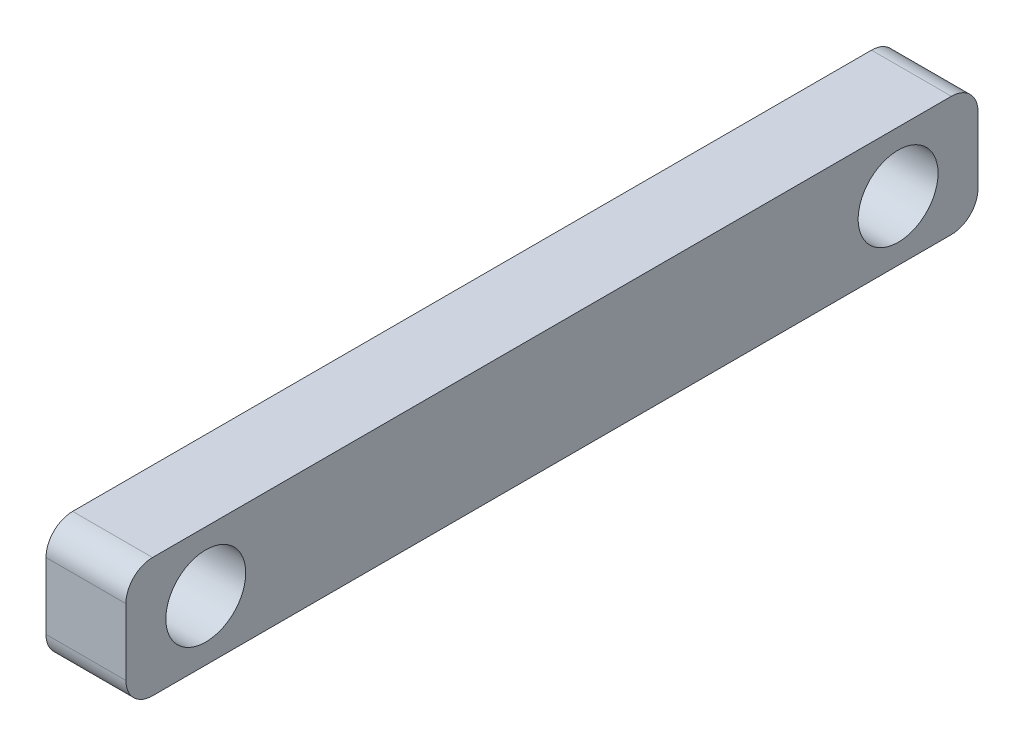
SolidWorks part; units mm, degrees
ref_plane "Alzado" through (0, 0, 0) normal (0, 0, 1) x (1, 0, 0)
ref_plane "Planta" through (0, 0, 0) normal (0, 1, 0) x (1, 0, 0)
ref_plane "Vista lateral" through (0, 0, 0) normal (1, 0, 0) x (0, 0, -1)
sketch "Croquis1" plane through (0, 0, 0) normal (1, 0, 0) x (0, 0, -1)
  line L0 (-15, 2.25) -> (15, 2.25)
  line L2 (-16, 0) -> (16, 0) construction
  line L3 (-16, 1.25) -> (-16, -1.25)
  line L4 (-15, -2.25) -> (15, -2.25)
  line L5 (16, 1.25) -> (16, -1.25)
  arc A0 (-16, -1.25) -> (-15, -2.25) centre (-15, -1.25) ccw
  arc A1 (-16, 1.25) -> (-15, 2.25) centre (-15, 1.25) cw
  arc A2 (15, -2.25) -> (16, -1.25) centre (15, -1.25) ccw
  arc A3 (15, 2.25) -> (16, 1.25) centre (15, 1.25) cw
  point P1 (0, 0)
  point P9 (-16, -2.25)
  point P13 (-16, 2.25)
  point P16 (16, -2.25)
  point P19 (16, 2.25)
  dimension "D3" = 1
  dimension "D4" = 1
  dimension "D1" = 2.25
  dimension "D2" = 32
extrude "Saliente-Extruir1" add sketch "Croquis1" along normal mid plane 3
sketch "Croquis2" plane through (0, 0, 0) normal (1, 0, 0) x (0, 0, -1)
  line L0 (-16, 1.25) -> (-16, -1.25) construction
  line L1 (16, -1.25) -> (16, 1.25) construction
  circle A0 centre (-13, 0) radius 1.5
  circle A1 centre (13, 0) radius 1.5
  dimension "D1" = 3
  dimension "D3" = 3
  dimension "D2" = 3
  dimension "D4" = 3
extrude "Cortar-Extruir1" cut sketch "Croquis2" against normal through all both and the other way through all
